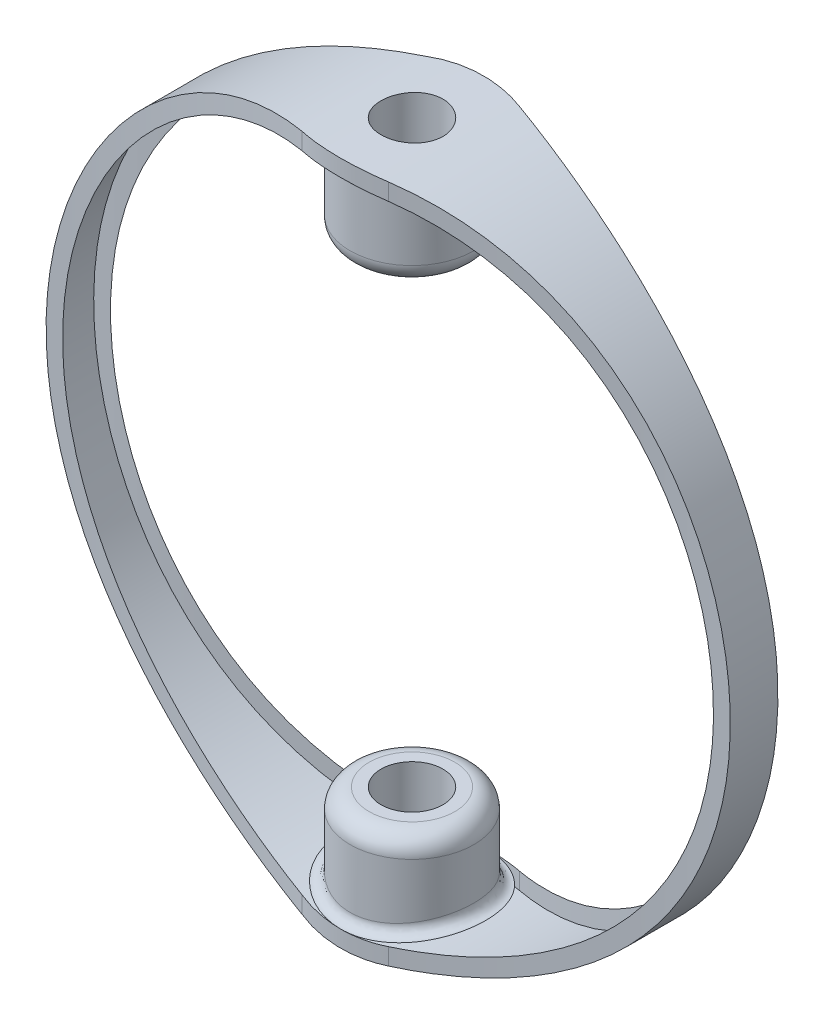
SolidWorks part; units mm, degrees
ref_plane "Front Plane" through (0, 0, 0) normal (0, 0, 1) x (1, 0, 0)
ref_plane "Top Plane" through (0, 0, 0) normal (0, 1, 0) x (1, 0, 0)
ref_plane "Right Plane" through (0, 0, 0) normal (1, 0, 0) x (0, 0, -1)
sketch "Sketch1" plane through (0, 0, 0) normal (0, 0, 1) x (1, 0, 0)
  circle A0 centre (0, 0) radius 35.9225
  circle A1 centre (0, 0) radius 34.1698
  dimension "D1" = 71.845
  dimension "D2" = 1.7527
extrude "Boss-Extrude1" add sketch "Sketch1" along normal blind 15
sketch "Sketch2" plane through (0, 0, 0) normal (0, 1, 0) x (1, 0, 0)
  line L0 (0, 0) -> (0, -15) construction
  line L1 (-35.9225, -15) -> (35.9225, -15) construction
  circle A1 centre (0, -7.5) radius 3.25
  circle A2 centre (0, -7.5) radius 6.5
  dimension "D1" = 6.5
  dimension "D2" = 13
extrude "Cut-Extrude1" cut sketch "Sketch2" against normal mid plane 100 contours A1
extrude "Boss-Extrude3" add sketch "Sketch2<4>" along normal mid plane 70
sketch "Sketch2<4>" plane through (0, 0, 0) normal (0, 1, 0) x (1, 0, 0) same geometry as "Sketch2"
extrude "Cut-Extrude4" cut sketch "Sketch2<7>" against normal mid plane 50
sketch "Sketch2<7>" plane through (0, 0, 0) normal (0, 1, 0) x (1, 0, 0) same geometry as "Sketch2"
sketch "Sketch4" plane through (0, 0, 0) normal (0, 0, -1) x (-1, 0, 0)
  line L0 (0, 35.9225) -> (0, -35.9225) construction
  circle A0 centre (0, 0) radius 35.9225 construction
  dimension "D1" = 71.845
sketch "Sketch7" plane through (0, -25, 0) normal (0, 1, 0) x (1, 0, 0)
  line L0 (35.9225, 0) -> (35.9225, -5)
  line L1 (35.9225, -15) -> (35.9225, 0) construction
  line L2 (35.9225, -15) -> (35.9225, -10)
  line L3 (-35.9225, -15) -> (-35.9225, -10)
  line L4 (-35.9225, 0) -> (-35.9225, -5)
  line L5 (-35.9225, 0) -> (-35.9225, -15) construction
  line L6 (35.9225, -15) -> (0, -15)
  line L7 (35.9225, 0) -> (0, 0)
  line L8 (0, 0) -> (-35.9225, 0)
  line L9 (0, -15) -> (-35.9225, -15)
  circle A0 centre (0, -7.5) radius 7.5
  arc A1 (-35.9225, -5) -> (-3.1302, -0.3093) centre (-35.9225, 111.9701) ccw
  arc A2 (-35.9225, -10) -> (-3.6772, -14.5696) centre (-35.9225, -126.0549) cw
  arc A3 (35.9225, -5) -> (4.0906, -0.5366) centre (35.9225, 110.7396) cw
  arc A4 (35.9225, -10) -> (4.0906, -14.4634) centre (35.9225, -125.7396) ccw
  ellipse E0 centre (0, -7.5) end of major axis (-11.0129, -7.5) minor radius 7.5
  dimension "D1" = 15
  dimension "D2" = 5
  dimension "D3" = 5
  dimension "D4" = 5
  dimension "D5" = 5
  dimension "D6" = 11.0129
extrude "Cut-Extrude5" cut sketch "Sketch7" against normal mid plane 200 contours E0 A3 L0 L7 | E0 L6 L2 A4 | E0 L8 L4 A1 | E0 A2 L3 L9 region at (23.2237, -25, 1.9999) region at (-23.18, -25, 2.0019) region at (23.2237, -25, 13.0001) region at (-23.2118, -25, 12.9996)
fillet "Fillet3" radius 2 1 edges at (0, 25, 14)
fillet "Fillet4" radius 2 1 edges at (0, -25, 14)
fillet "Fillet6" radius 1 2 edges at (-1.3641, -34.1426, 13.8553) (1.3641, 34.1426, 13.8553)
